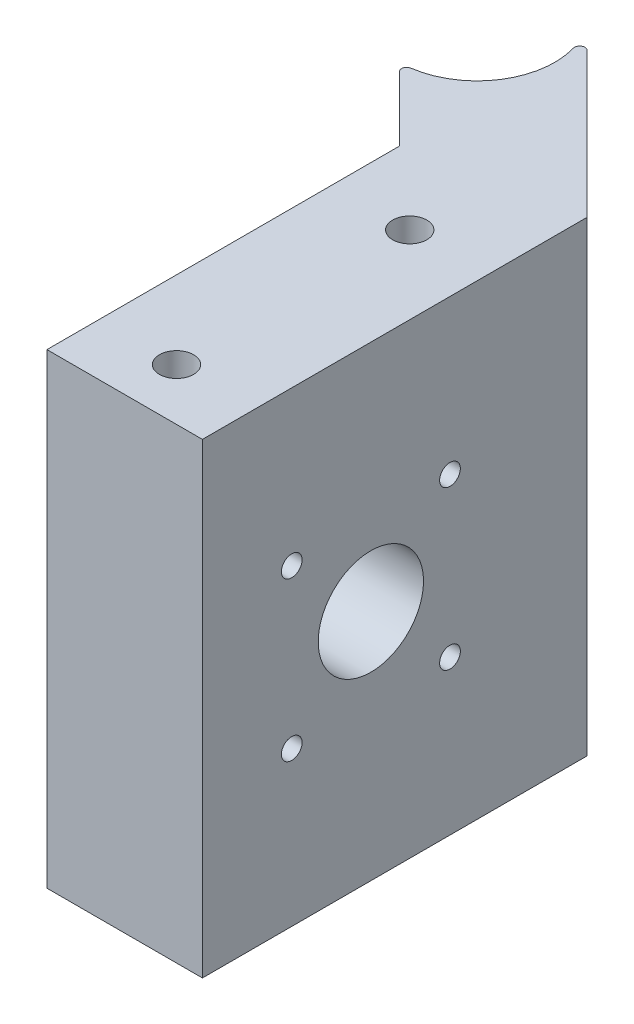
SolidWorks part; units mm, degrees
ref_plane "Front Plane" through (0, 0, 0) normal (0, 0, 1) x (1, 0, 0)
ref_plane "Top Plane" through (0, 0, 0) normal (0, 1, 0) x (1, 0, 0)
ref_plane "Right Plane" through (0, 0, 0) normal (1, 0, 0) x (0, 0, -1)
sketch "Sketch1" plane through (0, 0, 0) normal (0, 1, 0) x (1, 0, 0)
  line L0 (-14.5, 51) -> (7.5, 51) construction
  line L1 (7.5, 51) -> (7.5, 32.1066) construction
  line L2 (7.5, -5) -> (-7.5, -5)
  line L3 (-7.5, -5) -> (-7.5, 29)
  line L4 (-7.5, 36) -> (-14.5, 36) construction
  line L5 (0, 0) -> (0, -5) construction
  line L6 (-14.5, 36) -> (-7.5, 29)
  line L7 (-9.1967, 48.8033) -> (7.5, 32.1066)
  line L8 (-7.5, 29) -> (-7.5, 36) construction
  line L9 (7.5, 32.1066) -> (7.5, -5)
  circle A0 centre (0, 22.5) radius 1.65
  circle A1 centre (0, 0) radius 1.65
  arc A2 (-14.5, 36) -> (-9.1967, 48.8033) centre (-14.5, 43.5) ccw
  arc A3 (-9.1967, 48.8033) -> (-14.5, 51) centre (-14.5, 43.5) ccw construction
  dimension "D2" = 3.3
  dimension "D3" = 15
  dimension "D1" = 22.5
  dimension "D4" = 14.5
  dimension "D5" = 21
  dimension "D6" = 15
  dimension "D7" = 5
  dimension "D8" = 45
extrude "Boss-Extrude1" add sketch "Sketch1" along normal blind 45 contours A2 L6 L3 L2 L9 L7 A1 A0 region at (-0.8717, 0, -18.4654)
sketch "Sketch2" plane through (7.5, 0, 0) normal (1, 0, 0) x (0, 0, -1)
  line L0 (3.617, 30.133) -> (18.883, 14.867) construction
  line L1 (3.617, 30.133) -> (18.883, 30.133) construction
  line L2 (3.617, 30.133) -> (3.617, 14.867) construction
  line L3 (3.617, 14.867) -> (18.883, 14.867) construction
  line L4 (18.883, 30.133) -> (18.883, 14.867) construction
  line L5 (-5, 22.5) -> (11.25, 22.5) construction
  line L6 (-5, 45) -> (-5, 0) construction
  circle A0 centre (11.25, 22.5) radius 5.08
  circle A1 centre (3.617, 30.133) radius 1
  circle A2 centre (18.883, 30.133) radius 1
  circle A3 centre (18.883, 14.867) radius 1
  circle A4 centre (3.617, 14.867) radius 1
  dimension "D1" = 10.16
  dimension "D3" = 2
  dimension "D2" = 15.266
  dimension "D4" = 16.25
extrude "Cut-Extrude1" cut sketch "Sketch2" against normal up to next
fillet "Fillet1" radius 0.5 2 edges at (-9.1967, 22.5, -48.8033) (-14.5, 22.5, -36)
ref_plane "Plane1" through (0, 22.5, 0) normal (0, 1, 0) x (1, 0, 0)
sketch "Sketch3" plane through (0, 22.5, 0) normal (0, 1, 0) x (1, 0, 0)
  line L0 (-8.136, 37.136) -> (-2.8327, 42.4393)
  line L1 (-6.4581, 46.0647) -> (7.5, 32.1066) construction
  line L2 (-1.7721, 41.3787) -> (-7.0754, 36.0754)
  line L3 (-13.7263, 35.2263) -> (-7.5, 29) construction
  line L4 (-13.1083, 34.6083) -> (-11.842, 33.342)
  line L5 (-2.8327, 42.4393) -> (-1.7721, 41.3787)
  arc A0 (-13.1083, 34.6083) -> (-8.136, 37.136) centre (-14.5, 43.5) ccw
  arc A1 (-7.0754, 36.0754) -> (-11.842, 33.342) centre (-14.5, 43.5) cw
  dimension "D1" = 18
  dimension "D2" = 1.5
extrude "Cut-Extrude2" cut sketch "Sketch3" against normal mid plane 4
extrude "Cut-Extrude3" cut sketch "Sketch3<2>" against normal mid plane 4 from offset 17
sketch "Sketch3<2>" plane through (0, 22.5, 0) normal (0, 1, 0) x (1, 0, 0) same geometry as "Sketch3"
mirror "Mirror1" about plane through (0, 22.5, 0) normal (0, 1, 0) of "Cut-Extrude3"
